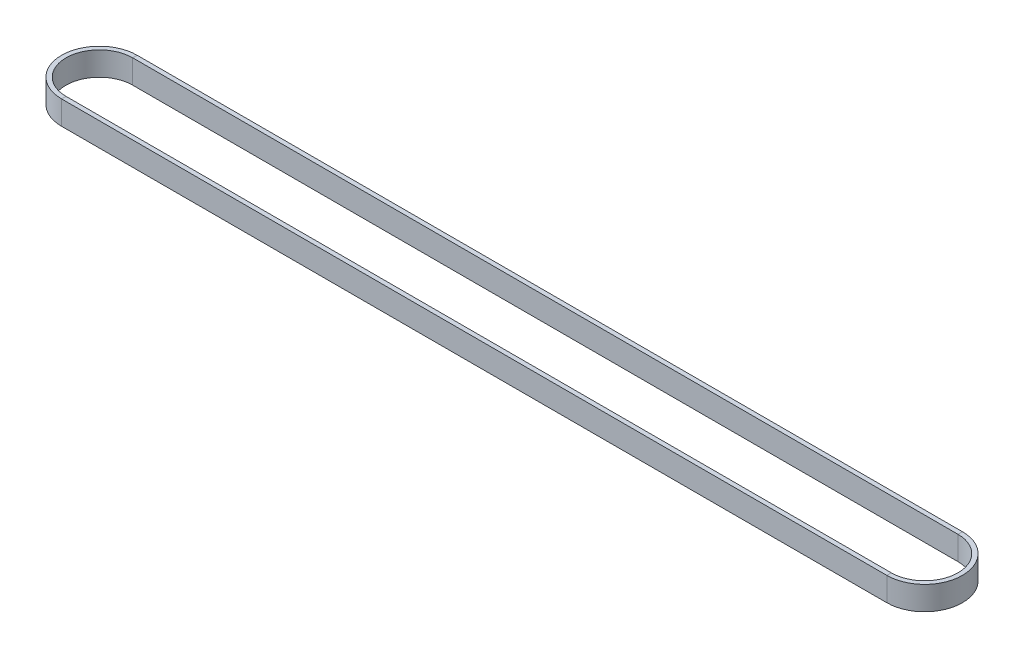
SolidWorks part; units mm, degrees
ref_plane "Front" through (0, 0, 0) normal (0, 0, 1) x (1, 0, 0)
ref_plane "Top" through (0, 0, 0) normal (0, 1, 0) x (1, 0, 0)
ref_plane "Right" through (0, 0, 0) normal (1, 0, 0) x (0, 0, -1)
sketch "Sketch1" plane through (0, 0, 0) normal (0, 1, 0) x (1, 0, 0)
  line L0 (0, 0) -> (353.5165, 0) construction
  line L1 (0, 15.24) -> (353.5165, 15.24)
  line L2 (0, -15.24) -> (353.5165, -15.24)
  arc A0 (0, 15.24) -> (0, -15.24) centre (0, 0) ccw
  arc A1 (353.5165, -15.24) -> (353.5165, 15.24) centre (353.5165, 0) ccw
  point P3 (176.7583, 0)
  dimension "D1" = 353.5165
  dimension "D2" = 30.48
sketch "Sketch2" plane through (0, 0, 0) normal (1, 0, 0) x (0, 0, -1)
  line L1 (-14.2875, -5.08) -> (-16.1925, -5.08)
  line L2 (-14.2875, -5.08) -> (-14.2875, 5.08)
  line L3 (-14.2875, 5.08) -> (-16.1925, 5.08)
  line L4 (-16.1925, -5.08) -> (-16.1925, 5.08)
  line L5 (-14.2875, -5.08) -> (-16.1925, 5.08) construction
  line L6 (-14.2875, 5.08) -> (-16.1925, -5.08) construction
  point P1 (-15.24, 0)
  dimension "D1" = 10.16
  dimension "D2" = 1.905
sweep "Sweep1" add profiles "Sketch2" path "Sketch1"
ref_axis "Axis1" through (0, 0, 0) along (0, 1, 0)
ref_axis "Axis2" through (353.5165, 0, 0) along (0, 1, 0)
